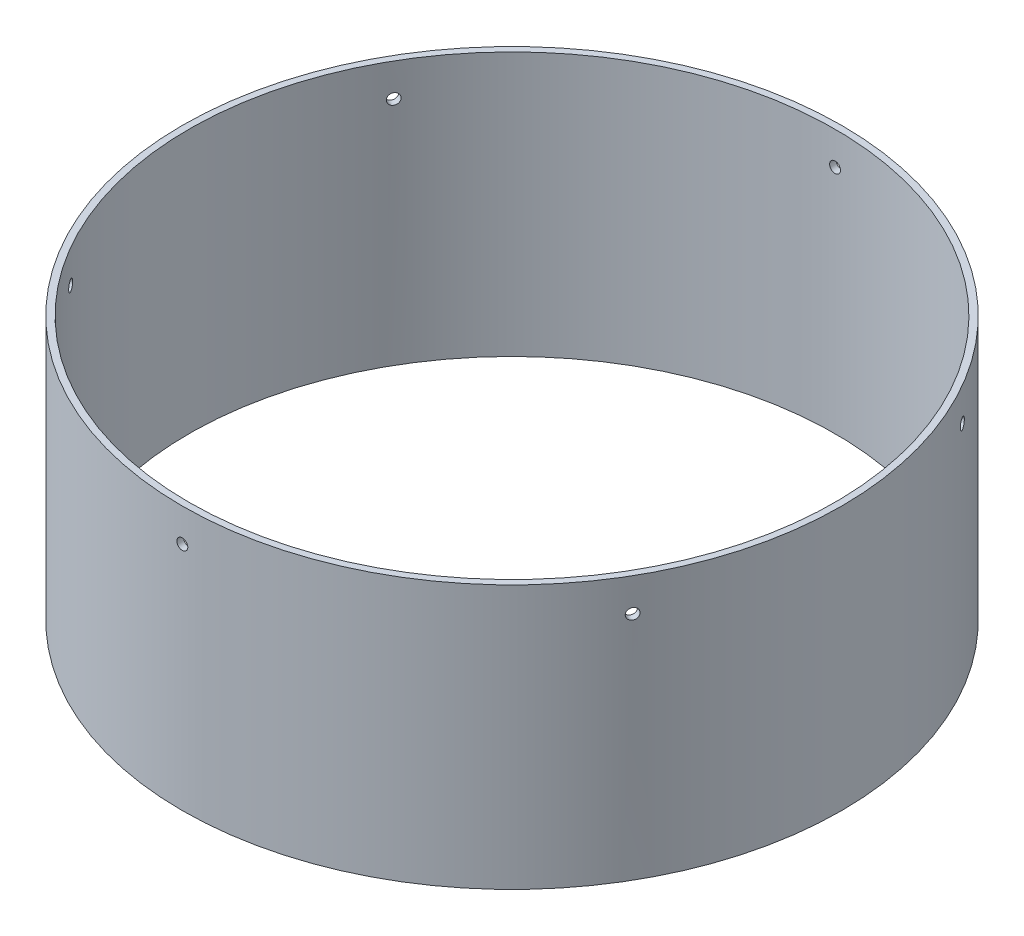
SolidWorks part; units mm, degrees
ref_plane "Front Plane" through (0, 0, 0) normal (0, 0, 1) x (1, 0, 0)
ref_plane "Top Plane" through (0, 0, 0) normal (0, 1, 0) x (1, 0, 0)
ref_plane "Right Plane" through (0, 0, 0) normal (1, 0, 0) x (0, 0, -1)
sketch "Sketch1" plane through (0, 0, 0) normal (0, 1, 0) x (1, 0, 0)
  circle A0 centre (0, 0) radius 100
  circle A1 centre (0, 0) radius 98
  dimension "D1" = 2
  dimension "D2" = 200
extrude "Boss-Extrude1" add sketch "Sketch1" along normal blind 80
sketch3d "3DSketch1"
  line L0 (0, 0, 0) -> (0, 80, 0) construction
  line L2 (-100, 80, 0) -> (100, 80, 0) construction
  circle A0 centre (0, 80, 0) radius 100 construction
  circle A1 centre (0, 70, 0) radius 1.65
  point P6 (0, 180, 0)
  point P11 (0, 70, 1.65)
  dimension "D1" = 3.3
  dimension "D2" = 10
sketch "Sketch2" plane through (0, 80, 0) normal (0, 1, 0) x (1, 0, 0)
  line L0 (0, 0) -> (0, -98) construction
  circle A0 centre (0, 0) radius 98 construction
extrude "Cut-Extrude1" cut sketch "3DSketch1" along direction (0, 0, 1) on the side against the normal through all and the other way through all
pattern_circular "CirPattern1" count 3 over 360 about axis through (0, 80, 0) along (0, -1, 0) of "Cut-Extrude1"
